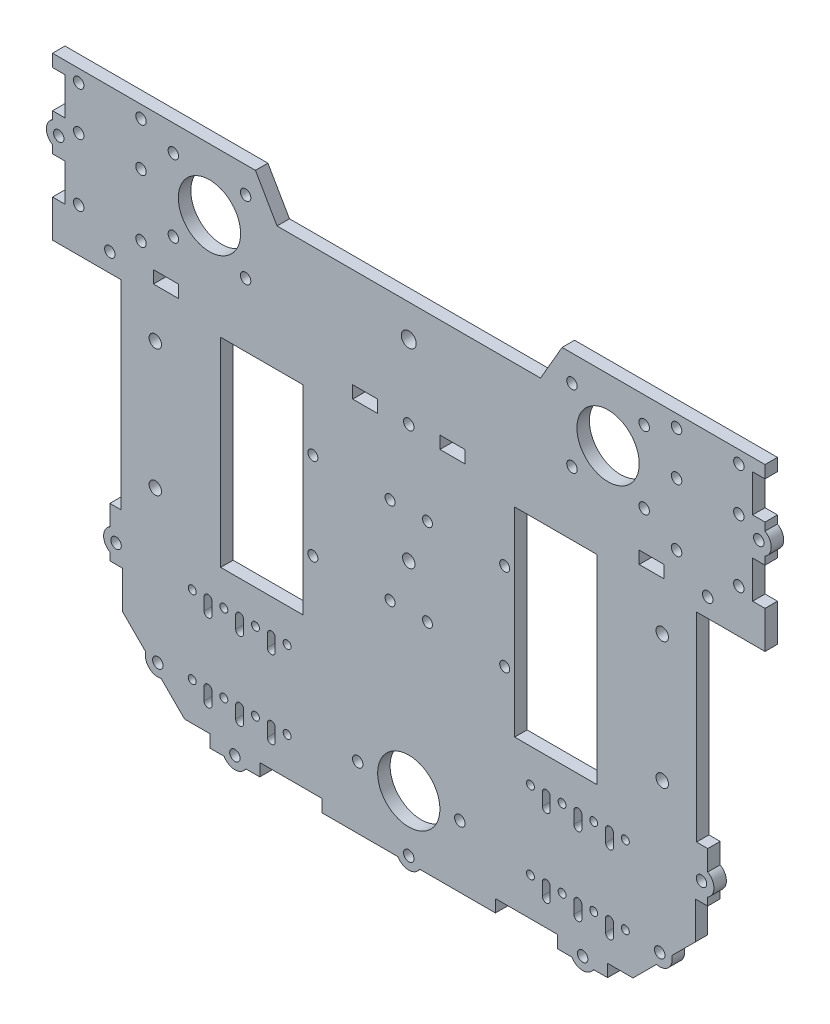
SolidWorks part; units mm, degrees
ref_plane "Front Plane" through (0, 0, 0) normal (0, 0, 1) x (1, 0, 0)
ref_plane "Top Plane" through (0, 0, 0) normal (0, 1, 0) x (1, 0, 0)
ref_plane "Right Plane" through (0, 0, 0) normal (1, 0, 0) x (0, 0, -1)
sketch "Sketch1" plane through (0, 0, 0) normal (0, 0, 1) x (1, 0, 0)
  line L1 (0, 0) -> (-240, 0)
  line L2 (0, 0) -> (0, 210)
  line L3 (0, 210) -> (-240, 210)
  line L4 (-240, 0) -> (-240, 210)
  dimension "D1" = 240
  dimension "D2" = 210
extrude "Boss-Extrude1" add sketch "Sketch1" along normal blind 5
sketch "Sketch2" plane through (0, 0, 5) normal (0, 0, 1) x (1, 0, 0)
  line L0 (-240, 210) -> (-240, 0) construction
  line L1 (-240, 145) -> (-162.5, 145)
  line L2 (-240, 145) -> (-240, 65)
  line L3 (-240, 65) -> (-162.5, 65)
  line L4 (-162.5, 145) -> (-162.5, 65)
  line L5 (-120, 210) -> (-120, 182.7983) construction
  line L6 (0, 210) -> (-240, 210) construction
  line L7 (-77.5, 145) -> (-77.5, 65)
  line L8 (0, 65) -> (-77.5, 65)
  line L9 (0, 145) -> (0, 65)
  line L10 (0, 145) -> (-77.5, 145)
  point P14 (-240, 105)
  point P15 (-162.5, 105)
  dimension "D1" = 80
  dimension "D2" = 77.5
extrude "Cut-Extrude1" cut sketch "Sketch2" against normal blind 5
sketch "Sketch3" plane through (0, 0, 5) normal (0, 0, 1) x (1, 0, 0)
  line L0 (-162.5, 145) -> (-240, 145) construction
  line L1 (-230.5, 145) -> (-213, 145)
  line L2 (-230.5, 145) -> (-230.5, 65)
  line L3 (-230.5, 65) -> (-213, 65)
  line L4 (-213, 145) -> (-213, 65)
  line L5 (-240, 65) -> (-162.5, 65) construction
  line L6 (-162.5, 65) -> (-162.5, 145) construction
  line L7 (-120, 210) -> (-120, 181.1057) construction
  line L8 (0, 210) -> (-240, 210) construction
  line L9 (-27, 145) -> (-27, 65)
  line L10 (-9.5, 65) -> (-27, 65)
  line L11 (-9.5, 145) -> (-9.5, 65)
  line L12 (-9.5, 145) -> (-27, 145)
  dimension "D1" = 17.5
  dimension "D2" = 68
extrude "Boss-Extrude2" add sketch "Sketch3" against normal blind 5
ref_plane "Plane1" through (-120, 0, 0) normal (1, 0, 0) x (0, 0, -1)
sketch "Sketch9" plane through (0, 0, 0) normal (0, 0, -1) x (-1, 0, 0)
  line L0 (240, 0) -> (0, 0) construction
  line L1 (170, 190) -> (220, 276.6025)
  line L2 (220, 276.6025) -> (170, 363.2051)
  line L3 (170, 363.2051) -> (70, 363.2051)
  line L4 (70, 363.2051) -> (20, 276.6025)
  line L5 (20, 276.6025) -> (70, 190)
  line L6 (70, 190) -> (170, 190)
  line L8 (0, 210) -> (240, 210) construction
  circle A0 centre (120, 276.6025) radius 86.6025 construction
  point P11 (120, 0)
  dimension "D1" = 200
  dimension "D2" = 20
extrude "Cut-Extrude8" cut sketch "Sketch9" against normal blind 5
sketch "Sketch10" plane through (-240, 0, 0) normal (-1, 0, 0) x (0, 0, 1)
  line L4 (0, 210) -> (0, 145)
  line L5 (0, 145) -> (5, 145)
  line L6 (5, 145) -> (5, 210)
  line L7 (5, 210) -> (0, 210)
  line L8 (0, 210) -> (0, 145)
  line L9 (0, 145) -> (5, 145)
  line L10 (5, 145) -> (5, 210)
  line L11 (5, 210) -> (0, 210)
  dimension "D1" = 0
extrude "Boss-Extrude3" add sketch "Sketch10" along normal blind 20
mirror "Mirror2" about plane through (-120, 0, 0) normal (1, 0, 0) of "Boss-Extrude3"
sketch "Sketch5" plane through (0, 0, 5) normal (0, 0, 1) x (1, 0, 0)
  line L0 (20, 210) -> (-58.453, 210) construction
  line L3 (12.5, 187.5) -> (0, 175) construction
  line L4 (0, 175) -> (-10.0719, 185.0719) construction
  line L5 (20, 210) -> (20, 145) construction
  circle A1 centre (0, 175) radius 11 construction
  circle A2 centre (12.5, 187.5) radius 2.1
  circle A5 centre (-12.5, 162.5) radius 2.1
  circle A6 centre (-12.5, 187.5) radius 2.1
  circle A7 centre (12.5, 162.5) radius 2.1
  circle A8 centre (12.5, 187.5) radius 2.1
  circle A9 centre (-12.5, 162.5) radius 2.1
  circle A10 centre (12.5, 162.5) radius 2.1
  circle A11 centre (-12.5, 187.5) radius 2.1
  circle A12 centre (-12.5, 205) radius 2.1
  circle A13 centre (12.5, 205) radius 2.1
  dimension "D1" = 35
  dimension "D2" = 12.5
  dimension "D3" = 12.5
  dimension "D4" = 22
  dimension "D5" = 4
  dimension "D6" = 4.2
  dimension "D7" = 5
  dimension "D8" = 20
  dimension "D9" = 5
  dimension "D10" = 4.2
  dimension "D11" = 4.2
  dimension "D12" = 12.5
  dimension "D13" = 12.5
extrude "Cut-Extrude9" cut sketch "Sketch5" against normal blind 10 contours A1 | A6 | A12 | A7 | A5 | A2 | A13 region at (-12.5, 162.5, 5) region at (-12.5, 187.5, 5) region at (12.5, 162.5, 5) region at (-12.5, 205, 5)
mirror "Mirror3" about plane through (-120, 0, 0) normal (1, 0, 0) of "Cut-Extrude9"
sketch "Sketch12" plane through (0, 0, 5) normal (0, 0, 1) x (1, 0, 0)
  line L0 (0, 0) -> (0, 65) construction
  line L1 (0, 10) -> (-5, 10)
  line L2 (0, 10) -> (0, 45.2)
  line L3 (0, 45.2) -> (-5, 45.2)
  line L4 (-5, 10) -> (-5, 45.2)
  line L5 (-240, 0) -> (0, 0) construction
  line L6 (-120, -2.75) -> (-120, 2.75) construction
  line L7 (-240, 45.2) -> (-235, 45.2)
  line L8 (-235, 10) -> (-235, 45.2)
  line L9 (-240, 10) -> (-235, 10)
  line L10 (-240, 10) -> (-240, 45.2)
  line L11 (-240, 65) -> (-240, 0) construction
  line L12 (-215, 0) -> (-154.8, 0)
  line L13 (-215, 0) -> (-215, 5)
  line L14 (-215, 5) -> (-154.8, 5)
  line L15 (-154.8, 0) -> (-154.8, 5)
  line L16 (-25, 5) -> (-85.2, 5)
  line L17 (-85.2, 0) -> (-85.2, 5)
  line L18 (-25, 0) -> (-85.2, 0)
  line L19 (-25, 0) -> (-25, 5)
  dimension "D1" = 35.2
  dimension "D2" = 5
  dimension "D3" = 10
  dimension "D4" = 5
  dimension "D5" = 60.2
  dimension "D6" = 25
extrude "Cut-Extrude11" cut sketch "Sketch12" against normal blind 10
sketch "Sketch15" plane through (0, 0, 0) normal (0, 0, -1) x (-1, 0, 0)
  line L0 (162.5, 105) -> (150.9995, 105) construction
  line L1 (162.5, 65) -> (162.5, 145) construction
  line L2 (143, 87.5) -> (143, 97.0195) construction
  line L3 (162.5, 65) -> (77.5, 65) construction
  line L4 (120, 65) -> (120, 101.8451) construction
  line L5 (97, 87.5) -> (97, 97.0195) construction
  line L6 (77.5, 105) -> (89.0005, 105) construction
  circle A0 centre (158.5, 87.5) radius 2
  circle A1 centre (158.5, 122.5) radius 2
  circle A2 centre (127.5, 122.5) radius 2
  circle A3 centre (127.5, 87.5) radius 2
  circle A4 centre (112.5, 87.5) radius 2
  circle A5 centre (112.5, 122.5) radius 2
  circle A6 centre (81.5, 122.5) radius 2
  circle A7 centre (81.5, 87.5) radius 2
  circle A8 centre (120, 105) radius 2.5
  point P6 (162.5, 105)
  dimension "D1" = 4
  dimension "D2" = 4
  dimension "D3" = 17.5
  dimension "D5" = 5
  dimension "D4" = 15.5
extrude "Cut-Extrude13" cut sketch "Sketch15" against normal blind 10
sketch "Sketch16" plane through (0, 0, 0) normal (0, 0, -1) x (-1, 0, 0)
  line L0 (27, 145) -> (9.5, 145) construction
  line L1 (9.5, 65) -> (27, 65) construction
  line L2 (18.25, 145) -> (18.25, 65) construction
  line L3 (18.25, 105) -> (30.55, 105) construction
  line L4 (120, 105) -> (120, 123.3727) construction
  line L5 (221.75, 105) -> (209.45, 105) construction
  circle A4 centre (18.25, 130.5) radius 2.5
  circle A5 centre (18.25, 79.5) radius 2.5
  circle A6 centre (221.75, 79.5) radius 2.5
  circle A7 centre (221.75, 130.5) radius 2.5
  point P12 (18.25, 105)
  dimension "D1" = 5
  dimension "D2" = 25.5
extrude "Cut-Extrude14" cut sketch "Sketch16" against normal blind 10
sketch "Sketch17" plane through (0, 0, 0) normal (0, 0, -1) x (-1, 0, 0)
  line L0 (40, 185) -> (57.7701, 167.2299) construction
  line L1 (-20, 210) -> (58.453, 210) construction
  line L2 (-20, 210) -> (-20, 145) construction
  line L3 (40, 185) -> (33.7078, 178.7078) construction
  line L4 (120, 190) -> (120, 162.3502) construction
  line L5 (70, 190) -> (170, 190) construction
  line L6 (200, 185) -> (206.2922, 178.7078) construction
  line L7 (200, 185) -> (182.2299, 167.2299) construction
  line L8 (200, 185) -> (206.2922, 178.7078) construction
  line L9 (200, 185) -> (182.2299, 167.2299) construction
  circle A0 centre (40, 185) radius 12.5
  circle A1 centre (54.4957, 170.5043) radius 2.1
  circle A2 centre (25.5043, 199.4957) radius 2.1
  circle A12 centre (54.4957, 199.4957) radius 2.1
  circle A13 centre (25.5043, 170.5043) radius 2.1
  circle A14 centre (54.4957, 170.5043) radius 2.1
  circle A15 centre (25.5043, 199.4957) radius 2.1
  circle A16 centre (25.5043, 170.5043) radius 2.1
  circle A17 centre (54.4957, 199.4957) radius 2.1
  circle A18 centre (185.5043, 199.4957) radius 2.1
  circle A19 centre (214.4957, 170.5043) radius 2.1
  circle A20 centre (214.4957, 199.4957) radius 2.1
  circle A21 centre (185.5043, 170.5043) radius 2.1
  circle A22 centre (214.4957, 170.5043) radius 2.1
  circle A23 centre (185.5043, 199.4957) radius 2.1
  circle A24 centre (200, 185) radius 12.5
  circle A25 centre (185.5043, 170.5043) radius 2.1
  circle A26 centre (214.4957, 199.4957) radius 2.1
  dimension "D1" = 25
  dimension "D2" = 4.2
  dimension "D3" = 20.5
  dimension "D4" = 25
  dimension "D5" = 60
  dimension "D6" = 45
  dimension "D7" = 4
extrude "Cut-Extrude15" cut sketch "Sketch17" against normal blind 5 contours A13 | A0 | A13 | A12 | A1 | A24 | A20 | A19 | A21 | A2 | A18 region at (-40, 185, 0) region at (-54.4957, 170.5043, 0) region at (-54.4957, 199.4957, 0) region at (-25.5043, 170.5043, 0) region at (-214.4957, 170.5043, 0) region at (-214.4957, 199.4957, 0) region at (-185.5043, 170.5043, 0) region at (-200, 185, 0)
sketch "Sketch18" plane through (0, 0, 5) normal (0, 0, 1) x (1, 0, 0)
  line L0 (-235, 30) -> (-210, 5)
  line L1 (-235, 10) -> (-235, 45.2) construction
  line L2 (-154.8, 5) -> (-215, 5) construction
  line L3 (-210, 5) -> (-235, 5)
  line L4 (-235, 5) -> (-235, 30)
  line L5 (-235, 10) -> (-240, 10)
  line L6 (-240, 10) -> (-240, 0)
  line L7 (-240, 0) -> (-215, 0)
  line L8 (-215, 0) -> (-215, 5)
  line L9 (-120, -2.75) -> (-120, 2.75) construction
  line L10 (-5, 5) -> (-5, 30)
  line L11 (-5, 30) -> (-30, 5)
  line L12 (-25, 0) -> (-25, 5)
  line L13 (0, 0) -> (-25, 0)
  line L14 (0, 10) -> (0, 0)
  line L15 (-5, 10) -> (0, 10)
  line L16 (-30, 5) -> (-5, 5)
  dimension "D1" = 25
  dimension "D2" = 25
extrude "Cut-Extrude17" cut sketch "Sketch18" against normal blind 10 contours L4 L3 L0 | L7 L8 L3 L4 L5 L6 | L11 L16 L10 | L16 L12 L13 L14 L15 L10 region at (-226.6667, 13.3333, 5) region at (-229.1667, 3.3333, 5) region at (-13.3333, 13.3333, 5) region at (-10.8333, 3.3333, 5)
sketch "Sketch19" plane through (0, 0, 0) normal (0, 0, -1) x (-1, 0, 0)
  line L0 (154.8, 0) -> (85.2, 0) construction
  line L1 (166.1126, 25) -> (84.2471, 25) construction
  line L2 (120, 25) -> (120, 31.0152) construction
  circle A0 centre (120, 25) radius 12.5
  circle A2 centre (99.5, 25) radius 2.1
  circle A4 centre (140.5, 25) radius 2.1
  point P4 (120, 0)
  dimension "D1" = 25
  dimension "D2" = 25
  dimension "D3" = 4.2
  dimension "D4" = 20.5
extrude "Cut-Extrude18" cut sketch "Sketch19" against normal blind 10
sketch "Sketch21" plane through (-260, 0, 0) normal (-1, 0, 0) x (0, 0, 1)
  line L4 (5, 210) -> (0, 210)
  line L5 (0, 210) -> (0, 145)
  line L6 (0, 145) -> (5, 145)
  line L7 (5, 145) -> (5, 210)
  line L8 (5, 210) -> (0, 210)
  line L9 (0, 210) -> (0, 145)
  line L10 (0, 145) -> (5, 145)
  line L11 (5, 145) -> (5, 210)
  dimension "D1" = 0
extrude "Cut-Extrude20" cut sketch "Sketch21" against normal blind 3
sketch "Sketch22" plane through (20, 0, 0) normal (1, 0, 0) x (0, 0, -1)
  line L4 (0, 210) -> (-5, 210)
  line L5 (-5, 210) -> (-5, 145)
  line L6 (-5, 145) -> (0, 145)
  line L7 (0, 145) -> (0, 210)
  line L8 (0, 210) -> (-5, 210)
  line L9 (-5, 210) -> (-5, 145)
  line L10 (-5, 145) -> (0, 145)
  line L11 (0, 145) -> (0, 210)
  dimension "D1" = 0
extrude "Cut-Extrude21" cut sketch "Sketch22" against normal blind 3
sketch "Sketch23" plane through (0, 0, 0) normal (0, 0, -1) x (-1, 0, 0)
  line L0 (154.8, 0) -> (85.2, 0) construction
  line L1 (124.3301, 0) -> (115.6699, 0) construction
  circle A0 centre (120, 2.5) radius 2.1
  arc A1 (124.3301, 0) -> (115.6699, 0) centre (120, 2.5) cw construction
  point P5 (120, 0)
  dimension "D1" = 4.2
  dimension "D2" = 2.5
  dimension "D3" = 5
extrude "Cut-Extrude22" cut sketch "Sketch23" against normal blind 10
sketch "Sketch24" plane through (0, 0, 0) normal (0, 0, -1) x (-1, 0, 0)
  line L0 (154.8, 0) -> (85.2, 0) construction
  line L1 (124.3301, 0) -> (115.6699, 0)
  arc A0 (124.3301, 0) -> (115.6699, 0) centre (120, 2.5) cw
  dimension "D1" = 5
extrude "Boss-Extrude4" add sketch "Sketch24" against normal blind 5
sketch "Sketch25" plane through (-17.5, 17.5, 0) normal (0.7071, -0.7071, 0) x (0, 0, -1)
  line L1 (12.2918, -37.7929) -> (-20.8331, -37.7929)
  line L2 (12.2918, -37.7929) -> (12.2918, 35.3561)
  line L3 (12.2918, 35.3561) -> (-20.8331, 35.3561)
  line L4 (-20.8331, -37.7929) -> (-20.8331, 35.3561)
ref_plane "Plane2" through (-120, 0, 0) normal (1, 0, 0) x (0, 0, -1)
sketch "Sketch26" plane through (0, 5, 0) normal (0, -1, 0) x (1, 0, 0)
  line L1 (-60.2, 5) -> (-40.2, 5)
  line L2 (-60.2, 5) -> (-60.2, 0)
  line L3 (-60.2, 0) -> (-40.2, 0)
  line L4 (-40.2, 5) -> (-40.2, 0)
  line L7 (-85.2, 0) -> (-85.2, 5) construction
  line L8 (-124.3301, 5) -> (-124.3301, 0) construction
  line L12 (-115.6699, 5) -> (-115.6699, 0) construction
  line L13 (-124.3301, 5) -> (-124.3301, 0) construction
  line L14 (-115.6699, 5) -> (-115.6699, 0) construction
  line L16 (-115.6699, 2.5) -> (-124.3301, 2.5) construction
  line L17 (-124.3301, 2.5) -> (-120, 2.5) construction
  line L18 (-120, 2.5) -> (-120, 11.7083) construction
  line L19 (-199.8, 5) -> (-199.8, 0)
  line L20 (-179.8, 0) -> (-199.8, 0)
  line L21 (-179.8, 5) -> (-179.8, 0)
  line L22 (-179.8, 5) -> (-199.8, 5)
  line M6 (-30, 5) -> (-85.2, 5)
  line M8 (-85.2, 0) -> (-30, 0)
  dimension "D1" = 20
  dimension "D2" = 25
extrude "Boss-Extrude5" add sketch "Sketch26" along normal blind 5 contours L4 L2 M6 M8 | L21 L22 L19 L20 region at (-50.2, 5, 2.5) region at (-189.8, 5, 2.5)
sketch "Sketch27" plane through (0, 0, 0) normal (0, 0, -1) x (-1, 0, 0)
  line L2 (120, 2.5) -> (120, 6.3371) construction
  circle A0 centre (50.2, 2.5) radius 2.1
  circle A1 centre (189.8, 2.5) radius 2.1
  dimension "D3" = 4.2
extrude "Cut-Extrude24" cut sketch "Sketch27" against normal blind 5
sketch "Sketch29" plane through (0, 0, 0) normal (0, 0, -1) x (-1, 0, 0)
  line L1 (194.1301, 0) -> (185.4699, 0)
  line L2 (120, 2.75) -> (120, -2.75) construction
  line L3 (45.8699, 0) -> (54.5301, 0)
  arc A0 (185.4699, 0) -> (194.1301, 0) centre (189.8, 2.5) ccw
  arc A1 (54.5301, 0) -> (45.8699, 0) centre (50.2, 2.5) cw
  dimension "D1" = 5
extrude "Boss-Extrude7" add sketch "Sketch29" against normal blind 5
sketch "Sketch30" plane through (-9.5, 0, 0) normal (1, 0, 0) x (0, 0, -1)
  line L4 (-5, 145) -> (-5, 65)
  line L5 (-5, 65) -> (0, 65)
  line L6 (0, 65) -> (0, 145)
  line L7 (0, 145) -> (-5, 145)
  line L8 (-5, 145) -> (-5, 65)
  line L9 (-5, 65) -> (0, 65)
  line L10 (0, 65) -> (0, 145)
  line L11 (0, 145) -> (-5, 145)
  dimension "D1" = 0
extrude "Boss-Extrude8" add sketch "Sketch30" along normal blind 5
sketch "Sketch31" plane through (-230.5, 0, 0) normal (-1, 0, 0) x (0, 0, 1)
  line L4 (5, 65) -> (5, 145)
  line L5 (5, 145) -> (0, 145)
  line L6 (0, 145) -> (0, 65)
  line L7 (0, 65) -> (5, 65)
  line L8 (5, 65) -> (5, 145)
  line L9 (5, 145) -> (0, 145)
  line L10 (0, 145) -> (0, 65)
  line L11 (0, 65) -> (5, 65)
  dimension "D1" = 0
extrude "Boss-Extrude9" add sketch "Sketch31" along normal blind 5
sketch "Sketch32" plane through (0, 0, 0) normal (0, 0, -1) x (-1, 0, 0)
  line L0 (5, 30) -> (30, 5) construction
  line L1 (17.5, 17.5) -> (24.3538, 24.3538) construction
  circle A0 centre (19.2678, 19.2678) radius 2.1
  dimension "D1" = 4.2
  dimension "D2" = 2.5
extrude "Cut-Extrude25" cut sketch "Sketch32" against normal blind 5
sketch "Sketch33" plane through (0, 0, 0) normal (0, 0, -1) x (-1, 0, 0)
  line L0 (5, 30) -> (30, 5) construction
  line L1 (20.5619, 14.4381) -> (14.4381, 20.5619)
  arc A0 (20.5619, 14.4381) -> (14.4381, 20.5619) centre (19.2678, 19.2678) cw
  dimension "D1" = 5
extrude "Boss-Extrude10" add sketch "Sketch33" against normal blind 5
ref_plane "Plane3" through (-120, 0, 0) normal (-1, 0, 0) x (0, 0, 1)
mirror "Mirror4" about plane through (-120, 0, 0) normal (-1, 0, 0) of "Boss-Extrude10", "Cut-Extrude25"
sketch "Sketch34" plane through (0, 0, 5) normal (0, 0, 1) x (1, 0, 0)
  line L2 (-70, 190) -> (-170, 190) construction
  circle A0 centre (-120, 182) radius 3
  point P4 (-120, 190)
  dimension "D1" = 6
  dimension "D3" = 8
extrude "Cut-Extrude26" cut sketch "Sketch34" against normal blind 5
sketch "Sketch35" plane through (0, 0, 0) normal (0, 0, -1) x (-1, 0, 0)
  line L0 (70, 190) -> (170, 190) construction
  line L1 (97.5, 155) -> (107.5, 155)
  line L2 (97.5, 155) -> (97.5, 150)
  line L3 (97.5, 150) -> (107.5, 150)
  line L4 (107.5, 155) -> (107.5, 150)
  line L5 (-17, 145) -> (-17, 210) construction
  line L6 (120, 190) -> (120, 169.3293) construction
  line L7 (132.5, 155) -> (132.5, 150)
  line L8 (142.5, 150) -> (132.5, 150)
  line L9 (142.5, 155) -> (142.5, 150)
  line L10 (142.5, 155) -> (132.5, 155)
  line L11 (107.5, 152.5) -> (132.5, 152.5) construction
  circle A0 centre (120, 152.5) radius 2.1
  point P6 (97.5, 152.5)
  dimension "D5" = 4.2
  dimension "D1" = 35
  dimension "D2" = 114.5
  dimension "D3" = 10
  dimension "D4" = 5
extrude "Cut-Extrude27" cut sketch "Sketch35" against normal blind 5
sketch "Sketch37" plane through (0, 45.2, 0) normal (0, -1, 0) x (1, 0, 0)
  line L4 (0, 0) -> (0, 5)
  line L5 (0, 5) -> (-5, 5)
  line L6 (-5, 5) -> (-5, 0)
  line L7 (-5, 0) -> (0, 0)
  line L8 (0, 0) -> (0, 5)
  line L9 (0, 5) -> (-5, 5)
  line L10 (-5, 5) -> (-5, 0)
  line L11 (-5, 0) -> (0, 0)
  dimension "D1" = 0
extrude "Boss-Extrude11" add sketch "Sketch37" along normal blind 0.2
sketch "Sketch38" plane through (0, 45.2, 0) normal (0, -1, 0) x (1, 0, 0)
  line L4 (-235, 0) -> (-235, 5)
  line L5 (-235, 5) -> (-240, 5)
  line L6 (-240, 5) -> (-240, 0)
  line L7 (-240, 0) -> (-235, 0)
  line L8 (-235, 0) -> (-235, 5)
  line L9 (-235, 5) -> (-240, 5)
  line L10 (-240, 5) -> (-240, 0)
  line L11 (-240, 0) -> (-235, 0)
  dimension "D1" = 0
extrude "Boss-Extrude12" add sketch "Sketch38" along normal blind 0.2
sketch "Sketch39" plane through (0, 0, 0) normal (0, 0, -1) x (-1, 0, 0)
  line L0 (5, 45) -> (0, 45) construction
  line L1 (0, 45) -> (0, 65) construction
  line L2 (120, 37.5) -> (120, 57.8422) construction
  line L3 (0, 56.8301) -> (0, 48.1699) construction
  line L4 (240, 56.8301) -> (240, 48.1699) construction
  circle A0 centre (2.5, 52.5) radius 2.1
  circle A1 centre (120, 25) radius 12.5 construction
  circle A2 centre (237.5, 52.5) radius 2.1
  arc A3 (0, 48.1699) -> (0, 56.8301) centre (2.5, 52.5) cw construction
  arc A4 (240, 48.1699) -> (240, 56.8301) centre (237.5, 52.5) ccw construction
  dimension "D1" = 4.2
  dimension "D2" = 7.5
  dimension "D3" = 2.5
  dimension "D4" = 5
extrude "Cut-Extrude28" cut sketch "Sketch39" against normal blind 5
sketch "Sketch40" plane through (0, 0, 0) normal (0, 0, -1) x (-1, 0, 0)
  line L0 (0, 45) -> (0, 65) construction
  line L1 (0, 56.8301) -> (0, 48.1699)
  line L2 (120, 37.5) -> (120, 52.5) construction
  line L3 (240, 56.8301) -> (240, 48.1699)
  arc A0 (0, 48.1699) -> (0, 56.8301) centre (2.5, 52.5) cw
  circle A1 centre (120, 25) radius 12.5 construction
  arc A2 (240, 48.1699) -> (240, 56.8301) centre (237.5, 52.5) ccw
  dimension "D1" = 5
extrude "Boss-Extrude13" add sketch "Sketch40" against normal blind 5
sketch "Sketch42" plane through (0, 0, 5) normal (0, 0, 1) x (1, 0, 0)
  line L0 (-81.5, 122.5) -> (-81.5, 87.5) construction
  line L1 (-81.5, 105) -> (-63.225, 105) construction
  line L2 (-71.1625, 51.5) -> (-71.1625, 20.25) construction
  line L3 (-71.1625, 35.875) -> (-81.5, 35.875) construction
  line L4 (-64.8125, 51.5) -> (-64.8125, 20.25) construction
  line L5 (-58.4625, 51.5) -> (-58.4625, 20.25) construction
  line L6 (-52.1125, 20.25) -> (-52.1125, 51.5) construction
  line L7 (-45.7625, 51.5) -> (-45.7625, 20.25) construction
  line L8 (-39.4125, 20.25) -> (-39.4125, 51.5) construction
  line L9 (-33.0625, 51.5) -> (-33.0625, 20.25) construction
  line L10 (17, 210) -> (17, 145) construction
  line L13 (17, 210) -> (-58.453, 210) construction
  line L14 (-64.8125, 51.5) -> (-64.8125, 46.5) construction
  line L15 (-63.225, 51.5) -> (-63.225, 46.5)
  line L16 (-66.4, 51.5) -> (-66.4, 46.5)
  line L17 (-52.1125, 51.5) -> (-52.1125, 46.5) construction
  line L18 (-50.525, 51.5) -> (-50.525, 46.5)
  line L19 (-53.7, 51.5) -> (-53.7, 46.5)
  line L20 (-39.4125, 51.5) -> (-39.4125, 46.5) construction
  line L21 (-37.825, 51.5) -> (-37.825, 46.5)
  line L22 (-41, 51.5) -> (-41, 46.5)
  line L23 (-64.8125, 20.25) -> (-64.8125, 15.25) construction
  line L24 (-63.225, 20.25) -> (-63.225, 15.25)
  line L25 (-66.4, 20.25) -> (-66.4, 15.25)
  line L26 (-52.1125, 20.25) -> (-52.1125, 15.25) construction
  line L27 (-50.525, 20.25) -> (-50.525, 15.25)
  line L28 (-53.7, 20.25) -> (-53.7, 15.25)
  line L29 (-39.4125, 20.25) -> (-39.4125, 15.25) construction
  line L30 (-37.825, 20.25) -> (-37.825, 15.25)
  line L31 (-41, 20.25) -> (-41, 15.25)
  line L32 (-120, -2.75) -> (-120, 2.75) construction
  line L33 (-206.9375, 51.5) -> (-206.9375, 20.25) construction
  line L34 (-200.5875, 20.25) -> (-200.5875, 51.5) construction
  line L35 (-194.2375, 51.5) -> (-194.2375, 20.25) construction
  line L36 (-187.8875, 20.25) -> (-187.8875, 51.5) construction
  line L37 (-181.5375, 51.5) -> (-181.5375, 20.25) construction
  line L38 (-175.1875, 51.5) -> (-175.1875, 20.25) construction
  line L39 (-168.8375, 35.875) -> (-158.5, 35.875) construction
  line L40 (-168.8375, 51.5) -> (-168.8375, 20.25) construction
  line L41 (-200.5875, 20.25) -> (-200.5875, 15.25) construction
  line L42 (-202.175, 20.25) -> (-202.175, 15.25)
  line L43 (-199, 20.25) -> (-199, 15.25)
  line L44 (-187.8875, 20.25) -> (-187.8875, 15.25) construction
  line L45 (-189.475, 20.25) -> (-189.475, 15.25)
  line L46 (-186.3, 20.25) -> (-186.3, 15.25)
  line L47 (-175.1875, 20.25) -> (-175.1875, 15.25) construction
  line L48 (-176.775, 20.25) -> (-176.775, 15.25)
  line L49 (-173.6, 20.25) -> (-173.6, 15.25)
  line L50 (-200.5875, 51.5) -> (-200.5875, 46.5) construction
  line L51 (-202.175, 51.5) -> (-202.175, 46.5)
  line L52 (-199, 51.5) -> (-199, 46.5)
  line L53 (-187.8875, 51.5) -> (-187.8875, 46.5) construction
  line L54 (-189.475, 51.5) -> (-189.475, 46.5)
  line L55 (-186.3, 51.5) -> (-186.3, 46.5)
  line L56 (-175.1875, 51.5) -> (-175.1875, 46.5) construction
  line L57 (-176.775, 51.5) -> (-176.775, 46.5)
  line L58 (-173.6, 51.5) -> (-173.6, 46.5)
  arc A2 (-63.225, 51.5) -> (-66.4, 51.5) centre (-64.8125, 51.5) ccw
  arc A3 (-66.4, 46.5) -> (-63.225, 46.5) centre (-64.8125, 46.5) ccw
  arc A4 (-50.525, 51.5) -> (-53.7, 51.5) centre (-52.1125, 51.5) ccw
  arc A5 (-53.7, 46.5) -> (-50.525, 46.5) centre (-52.1125, 46.5) ccw
  arc A6 (-37.825, 51.5) -> (-41, 51.5) centre (-39.4125, 51.5) ccw
  arc A7 (-41, 46.5) -> (-37.825, 46.5) centre (-39.4125, 46.5) ccw
  arc A8 (-63.225, 20.25) -> (-66.4, 20.25) centre (-64.8125, 20.25) ccw
  arc A9 (-66.4, 15.25) -> (-63.225, 15.25) centre (-64.8125, 15.25) ccw
  arc A10 (-50.525, 20.25) -> (-53.7, 20.25) centre (-52.1125, 20.25) ccw
  arc A11 (-53.7, 15.25) -> (-50.525, 15.25) centre (-52.1125, 15.25) ccw
  arc A12 (-37.825, 20.25) -> (-41, 20.25) centre (-39.4125, 20.25) ccw
  arc A13 (-41, 15.25) -> (-37.825, 15.25) centre (-39.4125, 15.25) ccw
  arc A14 (-179.95, 51.5) -> (-183.125, 51.5) centre (-181.5375, 51.5) cw
  arc A15 (-183.125, 51.5) -> (-179.95, 51.5) centre (-181.5375, 51.5) cw
  arc A16 (-173.6, 51.5) -> (-176.775, 51.5) centre (-175.1875, 51.5) cw
  arc A17 (-176.775, 51.5) -> (-173.6, 51.5) centre (-175.1875, 51.5) cw
  arc A18 (-167.25, 51.5) -> (-170.425, 51.5) centre (-168.8375, 51.5) cw
  arc A19 (-170.425, 51.5) -> (-167.25, 51.5) centre (-168.8375, 51.5) cw
  arc A20 (-189.475, 51.5) -> (-186.3, 51.5) centre (-187.8875, 51.5) cw
  arc A21 (-186.3, 51.5) -> (-189.475, 51.5) centre (-187.8875, 51.5) cw
  arc A22 (-195.825, 51.5) -> (-192.65, 51.5) centre (-194.2375, 51.5) cw
  arc A23 (-192.65, 51.5) -> (-195.825, 51.5) centre (-194.2375, 51.5) cw
  arc A24 (-202.175, 51.5) -> (-199, 51.5) centre (-200.5875, 51.5) cw
  arc A25 (-199, 51.5) -> (-202.175, 51.5) centre (-200.5875, 51.5) cw
  arc A26 (-205.35, 51.5) -> (-208.525, 51.5) centre (-206.9375, 51.5) cw
  arc A27 (-208.525, 51.5) -> (-205.35, 51.5) centre (-206.9375, 51.5) cw
  arc A28 (-69.575, 20.25) -> (-72.75, 20.25) centre (-71.1625, 20.25) ccw
  arc A29 (-72.75, 20.25) -> (-69.575, 20.25) centre (-71.1625, 20.25) ccw
  arc A30 (-63.225, 20.25) -> (-66.4, 20.25) centre (-64.8125, 20.25) ccw
  arc A31 (-66.4, 20.25) -> (-63.225, 20.25) centre (-64.8125, 20.25) ccw
  arc A32 (-56.875, 20.25) -> (-60.05, 20.25) centre (-58.4625, 20.25) ccw
  arc A33 (-60.05, 20.25) -> (-56.875, 20.25) centre (-58.4625, 20.25) ccw
  arc A34 (-50.525, 20.25) -> (-53.7, 20.25) centre (-52.1125, 20.25) ccw
  arc A35 (-53.7, 20.25) -> (-50.525, 20.25) centre (-52.1125, 20.25) ccw
  arc A36 (-44.175, 20.25) -> (-47.35, 20.25) centre (-45.7625, 20.25) ccw
  arc A37 (-47.35, 20.25) -> (-44.175, 20.25) centre (-45.7625, 20.25) ccw
  arc A38 (-37.825, 20.25) -> (-41, 20.25) centre (-39.4125, 20.25) ccw
  arc A39 (-41, 20.25) -> (-37.825, 20.25) centre (-39.4125, 20.25) ccw
  arc A40 (-31.475, 20.25) -> (-34.65, 20.25) centre (-33.0625, 20.25) ccw
  arc A41 (-34.65, 20.25) -> (-31.475, 20.25) centre (-33.0625, 20.25) ccw
  arc A42 (-31.475, 51.5) -> (-34.65, 51.5) centre (-33.0625, 51.5) ccw
  arc A43 (-34.65, 51.5) -> (-31.475, 51.5) centre (-33.0625, 51.5) ccw
  arc A44 (-41, 51.5) -> (-37.825, 51.5) centre (-39.4125, 51.5) ccw
  arc A45 (-37.825, 51.5) -> (-41, 51.5) centre (-39.4125, 51.5) ccw
  arc A46 (-47.35, 51.5) -> (-44.175, 51.5) centre (-45.7625, 51.5) ccw
  arc A47 (-44.175, 51.5) -> (-47.35, 51.5) centre (-45.7625, 51.5) ccw
  arc A48 (-53.7, 51.5) -> (-50.525, 51.5) centre (-52.1125, 51.5) ccw
  arc A49 (-50.525, 51.5) -> (-53.7, 51.5) centre (-52.1125, 51.5) ccw
  arc A50 (-69.575, 51.5) -> (-72.75, 51.5) centre (-71.1625, 51.5) ccw
  arc A51 (-72.75, 51.5) -> (-69.575, 51.5) centre (-71.1625, 51.5) ccw
  arc A52 (-63.225, 51.5) -> (-66.4, 51.5) centre (-64.8125, 51.5) ccw
  arc A53 (-66.4, 51.5) -> (-63.225, 51.5) centre (-64.8125, 51.5) ccw
  arc A54 (-56.875, 51.5) -> (-60.05, 51.5) centre (-58.4625, 51.5) ccw
  arc A55 (-60.05, 51.5) -> (-56.875, 51.5) centre (-58.4625, 51.5) ccw
  arc A56 (-205.35, 20.25) -> (-208.525, 20.25) centre (-206.9375, 20.25) cw
  arc A57 (-208.525, 20.25) -> (-205.35, 20.25) centre (-206.9375, 20.25) cw
  arc A58 (-199, 20.25) -> (-202.175, 20.25) centre (-200.5875, 20.25) cw
  arc A59 (-202.175, 20.25) -> (-199, 20.25) centre (-200.5875, 20.25) cw
  arc A60 (-192.65, 20.25) -> (-195.825, 20.25) centre (-194.2375, 20.25) cw
  arc A61 (-195.825, 20.25) -> (-192.65, 20.25) centre (-194.2375, 20.25) cw
  arc A62 (-186.3, 20.25) -> (-189.475, 20.25) centre (-187.8875, 20.25) cw
  arc A63 (-189.475, 20.25) -> (-186.3, 20.25) centre (-187.8875, 20.25) cw
  arc A64 (-179.95, 20.25) -> (-183.125, 20.25) centre (-181.5375, 20.25) cw
  arc A65 (-183.125, 20.25) -> (-179.95, 20.25) centre (-181.5375, 20.25) cw
  arc A66 (-173.6, 20.25) -> (-176.775, 20.25) centre (-175.1875, 20.25) cw
  arc A67 (-176.775, 20.25) -> (-173.6, 20.25) centre (-175.1875, 20.25) cw
  arc A68 (-167.25, 20.25) -> (-170.425, 20.25) centre (-168.8375, 20.25) cw
  arc A69 (-170.425, 20.25) -> (-167.25, 20.25) centre (-168.8375, 20.25) cw
  arc A70 (-202.175, 20.25) -> (-199, 20.25) centre (-200.5875, 20.25) cw
  arc A71 (-199, 15.25) -> (-202.175, 15.25) centre (-200.5875, 15.25) cw
  arc A72 (-189.475, 20.25) -> (-186.3, 20.25) centre (-187.8875, 20.25) cw
  arc A73 (-186.3, 15.25) -> (-189.475, 15.25) centre (-187.8875, 15.25) cw
  arc A74 (-176.775, 20.25) -> (-173.6, 20.25) centre (-175.1875, 20.25) cw
  arc A75 (-173.6, 15.25) -> (-176.775, 15.25) centre (-175.1875, 15.25) cw
  arc A76 (-202.175, 51.5) -> (-199, 51.5) centre (-200.5875, 51.5) cw
  arc A77 (-199, 46.5) -> (-202.175, 46.5) centre (-200.5875, 46.5) cw
  arc A78 (-189.475, 51.5) -> (-186.3, 51.5) centre (-187.8875, 51.5) cw
  arc A79 (-186.3, 46.5) -> (-189.475, 46.5) centre (-187.8875, 46.5) cw
  arc A80 (-176.775, 51.5) -> (-173.6, 51.5) centre (-175.1875, 51.5) cw
  arc A81 (-173.6, 46.5) -> (-176.775, 46.5) centre (-175.1875, 46.5) cw
  point P22 (-64.8125, 35.875)
  point P23 (-58.4625, 35.875)
  point P28 (-52.1125, 35.875)
  point P29 (-45.7625, 35.875)
  point P34 (-39.4125, 35.875)
  point P35 (-33.0625, 35.875)
  point P52 (-64.8125, 49)
  point P70 (-52.1125, 49)
  point P86 (-39.4125, 49)
  point P92 (-64.8125, 17.75)
  point P98 (-52.1125, 17.75)
  point P104 (-39.4125, 17.75)
  point P158 (-200.5875, 17.75)
  point P162 (-187.8875, 17.75)
  point P166 (-175.1875, 17.75)
  point P170 (-200.5875, 49)
  point P174 (-187.8875, 49)
  point P178 (-175.1875, 49)
  dimension "D1" = 1.5875
  dimension "D10" = 31.25
  dimension "D2" = 36
  dimension "D3" = 50.0625
  dimension "D4" = 56.4125
  dimension "D5" = 62.7625
  dimension "D6" = 69.1125
  dimension "D7" = 75.4625
  dimension "D8" = 81.8125
  dimension "D9" = 88.1625
  dimension "D11" = 5
  dimension "D12" = 5
extrude "Cut-Extrude29" cut sketch "Sketch42" against normal blind 10 contours A6 A44 | A44 L22 A7 L21 | A46 A47 | A4 A48 | A54 A55 | A2 A53 | A50 A51 | A53 L16 A3 L15 | A48 L19 A5 L18 | A43 A42 | A41 A40 | L30 A13 L31 A12 | A37 A36 | L28 A11 L27 A10 | A33 A32 | L25 A9 L24 A8 | A29 A28 region at (-64.8125, 51.5, 5) region at (-64.8125, 47.7532, 5) region at (-52.1125, 51.5, 5) region at (-52.1125, 47.7532, 5) region at (-39.4125, 51.5, 5) region at (-39.4125, 47.7532, 5) region at (-45.7625, 51.5, 5) region at (-71.1625, 51.5, 5) region at (-58.4625, 51.5, 5)
sketch "Sketch43" plane through (-257, 0, 0) normal (-1, 0, 0) x (0, 0, 1)
  line L4 (5, 145) -> (5, 210)
  line L5 (5, 210) -> (0, 210)
  line L6 (0, 210) -> (0, 145)
  line L7 (0, 145) -> (5, 145)
  line L8 (5, 145) -> (5, 210)
  line L9 (5, 210) -> (0, 210)
  line L10 (0, 210) -> (0, 145)
  line L11 (0, 145) -> (5, 145)
  dimension "D1" = 0
extrude "Boss-Extrude14" add sketch "Sketch43" along normal blind 6
sketch "Sketch44" plane through (17, 0, 0) normal (1, 0, 0) x (0, 0, -1)
  line L4 (0, 145) -> (0, 210)
  line L5 (0, 210) -> (-5, 210)
  line L6 (-5, 210) -> (-5, 145)
  line L7 (-5, 145) -> (0, 145)
  line L8 (0, 145) -> (0, 210)
  line L9 (0, 210) -> (-5, 210)
  line L10 (-5, 210) -> (-5, 145)
  line L11 (-5, 145) -> (0, 145)
  dimension "D1" = 0
extrude "Boss-Extrude15" add sketch "Sketch44" along normal blind 6
sketch "Sketch45" plane through (0, 210, 0) normal (0, 1, 0) x (1, 0, 0)
  line L4 (-181.547, 0) -> (-263, 0)
  line L5 (-263, 0) -> (-263, -5)
  line L6 (-263, -5) -> (-181.547, -5)
  line L7 (-181.547, -5) -> (-181.547, 0)
  line L8 (-181.547, 0) -> (-263, 0)
  line L9 (-263, 0) -> (-263, -5)
  line L10 (-263, -5) -> (-181.547, -5)
  line L11 (-181.547, -5) -> (-181.547, 0)
  dimension "D1" = 0
extrude "Boss-Extrude16" [suppressed] add sketch "Sketch45" along normal blind 6
sketch "Sketch46" plane through (0, 210, 0) normal (0, 1, 0) x (1, 0, 0)
  line L4 (-58.453, -5) -> (23, -5)
  line L5 (23, -5) -> (23, 0)
  line L6 (23, 0) -> (-58.453, 0)
  line L7 (-58.453, 0) -> (-58.453, -5)
  line L8 (-58.453, -5) -> (23, -5)
  line L9 (23, -5) -> (23, 0)
  line L10 (23, 0) -> (-58.453, 0)
  line L11 (-58.453, 0) -> (-58.453, -5)
  dimension "D1" = 0
extrude "Boss-Extrude17" [suppressed] add sketch "Sketch46" along normal blind 6
sketch "Sketch47" [suppressed] plane through (0, 0, 5) normal (0, 0, 1) x (1, 0, 0)
  line L0 (-181.547, 210) -> (-185.0111, 216)
  line L1 (-263, 216) -> (-181.547, 216) construction
  line L2 (-185.0111, 216) -> (-181.547, 216)
  line L3 (-181.547, 216) -> (-181.547, 210)
  line L4 (-120, 182) -> (-120, 205.4993) construction
  line L5 (-58.453, 216) -> (-58.453, 210)
  line L6 (-54.9889, 216) -> (-58.453, 216)
  line L7 (-58.453, 210) -> (-54.9889, 216)
extrude "Cut-Extrude30" [suppressed] cut sketch "Sketch47" against normal blind 6
sketch "Sketch48" plane through (-213, 0, 0) normal (1, 0, 0) x (0, 0, -1)
  line L4 (-5, 145) -> (-5, 65)
  line L5 (-5, 65) -> (0, 65)
  line L6 (0, 65) -> (0, 145)
  line L7 (0, 145) -> (-5, 145)
  line L8 (-5, 145) -> (-5, 65)
  line L9 (-5, 65) -> (0, 65)
  line L10 (0, 65) -> (0, 145)
  line L11 (0, 145) -> (-5, 145)
  dimension "D1" = 0
extrude "Boss-Extrude18" [suppressed] add sketch "Sketch48" along normal blind 10
sketch "Sketch49" plane through (-27, 0, 0) normal (-1, 0, 0) x (0, 0, 1)
  line L4 (5, 65) -> (5, 145)
  line L5 (5, 145) -> (0, 145)
  line L6 (0, 145) -> (0, 65)
  line L7 (0, 65) -> (5, 65)
  line L8 (5, 65) -> (5, 145)
  line L9 (5, 145) -> (0, 145)
  line L10 (0, 145) -> (0, 65)
  line L11 (0, 65) -> (5, 65)
  dimension "D1" = 0
extrude "Boss-Extrude19" [suppressed] add sketch "Sketch49" along normal blind 10
sketch "Sketch50" [suppressed] plane through (0, 0, 5) normal (0, 0, 1) x (1, 0, 0)
  line L0 (23, 216) -> (23, 145) construction
  line L1 (23, 188.5) -> (18, 188.5)
  line L2 (23, 188.5) -> (23, 208.5)
  line L3 (23, 208.5) -> (18, 208.5)
  line L4 (18, 188.5) -> (18, 208.5)
  line L5 (-54.9889, 216) -> (23, 216) construction
  line L6 (18, 210.05) -> (18, 156.25) construction
  line L7 (23, 158.5) -> (18, 158.5)
  line L8 (23, 158.5) -> (23, 178.5)
  line L9 (23, 178.5) -> (18, 178.5)
  line L10 (18, 158.5) -> (18, 178.5)
  dimension "D1" = 5
  dimension "D2" = 7.5
  dimension "D3" = 20
  dimension "D4" = 20
  dimension "D5" = 10
extrude "Cut-Extrude31" [suppressed] cut sketch "Sketch50" against normal blind 5
ref_plane "Plane4" through (-120, 0, 0) normal (1, 0, 0) x (0, 0, -1)
mirror "Mirror5" [suppressed] about plane through (-120, 0, 0) normal (1, 0, 0)
sketch "Sketch51" [suppressed] plane through (0, 0, 5) normal (0, 0, 1) x (1, 0, 0)
  line L0 (-37, 65) -> (-37, 145) construction
  line L1 (-17.5, 150) -> (-27.5, 150)
  line L2 (-17.5, 150) -> (-17.5, 155)
  line L3 (-17.5, 155) -> (-27.5, 155)
  line L4 (-27.5, 150) -> (-27.5, 155)
  line L5 (-37, 145) -> (-77.5, 145) construction
  line L6 (-120, 190) -> (-120, 166.8051) construction
  line L7 (-70, 190) -> (-170, 190) construction
  line L8 (-212.5, 150) -> (-212.5, 155)
  line L9 (-222.5, 155) -> (-212.5, 155)
  line L10 (-222.5, 150) -> (-222.5, 155)
  line L11 (-222.5, 150) -> (-212.5, 150)
  dimension "D1" = 10
  dimension "D2" = 5
  dimension "D3" = 9.5
  dimension "D4" = 5
extrude "Cut-Extrude32" [suppressed] cut sketch "Sketch51" against normal blind 5
sketch "Sketch52" [suppressed] plane through (0, 216, 0) normal (0, 1, 0) x (1, 0, 0)
  line L4 (-185.0111, -5) -> (-185.0111, 0)
  line L5 (-185.0111, 0) -> (-263, 0)
  line L6 (-263, 0) -> (-263, -5)
  line L7 (-263, -5) -> (-185.0111, -5)
  line L8 (-185.0111, -5) -> (-185.0111, 0)
  line L9 (-185.0111, 0) -> (-263, 0)
  line L10 (-263, 0) -> (-263, -5)
  line L11 (-263, -5) -> (-185.0111, -5)
  line L12 (-54.9889, 0) -> (-54.9889, -5)
  line L13 (-54.9889, -5) -> (23, -5)
  line L14 (23, -5) -> (23, 0)
  line L15 (23, 0) -> (-54.9889, 0)
  line L16 (-54.9889, 0) -> (-54.9889, -5)
  line L17 (-54.9889, -5) -> (23, -5)
  line L18 (23, -5) -> (23, 0)
  line L19 (23, 0) -> (-54.9889, 0)
  dimension "D1" = 0
  dimension "D2" = 0
extrude "Boss-Extrude20" [suppressed] add sketch "Sketch52" along normal blind 5
sketch "Sketch53" [suppressed] plane through (0, 0, 5) normal (0, 0, 1) x (1, 0, 0)
  line L0 (-185.0111, 216) -> (-187.8979, 221)
  line L1 (-263, 221) -> (-185.0111, 221) construction
  line L2 (-187.8979, 221) -> (-185.0111, 221)
  line L3 (-185.0111, 221) -> (-185.0111, 216)
  line L4 (-120, 190) -> (-120, 205.7472) construction
  line L5 (-70, 190) -> (-170, 190) construction
  line L6 (-54.9889, 221) -> (-54.9889, 216)
  line L7 (-52.1021, 221) -> (-54.9889, 221)
  line L8 (-54.9889, 216) -> (-52.1021, 221)
extrude "Cut-Extrude33" [suppressed] cut sketch "Sketch53" against normal blind 5
sketch "Sketch54" plane through (0, 0, 0) normal (0, 0, -1) x (-1, 0, 0)
  line L0 (27, 145) -> (77.5, 145) construction
  line L1 (17.5, 155) -> (27.5, 155)
  line L2 (17.5, 155) -> (17.5, 150)
  line L3 (17.5, 150) -> (27.5, 150)
  line L4 (27.5, 155) -> (27.5, 150)
  line L5 (4.5, 65) -> (4.5, 145) construction
  line L6 (120, 152.5) -> (120, 138.2924) construction
  line L7 (212.5, 155) -> (212.5, 150)
  line L8 (222.5, 150) -> (212.5, 150)
  line L9 (222.5, 155) -> (222.5, 150)
  line L10 (222.5, 155) -> (212.5, 155)
  dimension "D1" = 10
  dimension "D2" = 5
  dimension "D3" = 5
  dimension "D4" = 13
extrude "Cut-Extrude34" cut sketch "Sketch54" against normal blind 5
sketch "Sketch55" [suppressed] plane through (0, 221, 0) normal (0, 1, 0) x (1, 0, 0)
  line L0 (-52.1021, -5) -> (23, -5) construction
  line L1 (23, 0) -> (13, 0)
  line L2 (23, 0) -> (23, -5)
  line L3 (23, -5) -> (13, -5)
  line L4 (13, 0) -> (13, -5)
  line L5 (23, 0) -> (-52.1021, 0) construction
  line L6 (-7, 0) -> (-17, 0)
  line L7 (-7, 0) -> (-7, -5)
  line L8 (-7, -5) -> (-17, -5)
  line L9 (-17, 0) -> (-17, -5)
  line L10 (-70, -5) -> (-170, -5) construction
  line L11 (-70, -5) -> (-170, -5)
  line L12 (-120, -5) -> (-120, 10.6636) construction
  line L13 (-223, 0) -> (-223, -5)
  line L14 (-233, -5) -> (-223, -5)
  line L15 (-233, 0) -> (-233, -5)
  line L16 (-233, 0) -> (-223, 0)
  line L17 (-253, 0) -> (-253, -5)
  line L18 (-263, -5) -> (-253, -5)
  line L19 (-263, 0) -> (-263, -5)
  line L20 (-263, 0) -> (-253, 0)
  line M7 (-52.1021, -5) -> (23, -5)
  line M8 (23, -5) -> (23, 0)
  line M9 (23, 0) -> (-52.1021, 0)
  dimension "D1" = 10
  dimension "D2" = 10
  dimension "D3" = 20
extrude "Cut-Extrude35" [suppressed] cut sketch "Sketch55" against normal blind 5 contours L9 L7 M9 M7 | L4 M9 M7 M8 | L16 L15 L14 L13 | L20 L19 L18 L17
sketch "Sketch56" plane through (0, 0, 0) normal (0, 0, -1) x (-1, 0, 0)
  line L0 (-23, 145) -> (-23, 210) construction
  line L1 (-23, 210) -> (58.453, 210) construction
  line L2 (-23, 160) -> (-18.0205, 160)
  line L3 (-23, 160) -> (-23, 175)
  line L4 (-23, 175) -> (-18.0205, 175)
  line L5 (-18.0205, 160) -> (-18.0205, 175)
  line L6 (-23, 190) -> (-18.0205, 190)
  line L7 (-23, 190) -> (-23, 205)
  line L8 (-23, 205) -> (-18.0205, 205)
  line L9 (-18.0205, 190) -> (-18.0205, 205)
  dimension "D1" = 15
  dimension "D2" = 15
  dimension "D3" = 15
  dimension "D4" = 5
extrude "Cut-Extrude36" cut sketch "Sketch56" against normal blind 5
mirror "Mirror6" about plane through (-120, 0, 0) normal (1, 0, 0) of "Cut-Extrude36"
sketch "Sketch57" plane through (0, 0, 0) normal (0, 0, -1) x (-1, 0, 0)
  line L0 (222.5, 150) -> (222.5, 155) construction
  line L1 (222.5, 155) -> (212.5, 155) construction
  line L2 (120, 150.4) -> (120, 136.6161) construction
  circle A0 centre (240, 152.5) radius 2.1
  circle A1 centre (120, 152.5) radius 2.1 construction
  circle A2 centre (0, 152.5) radius 2.1
  dimension "D1" = 4.2
  dimension "D2" = 17.5
  dimension "D3" = 2.5
extrude "Cut-Extrude37" cut sketch "Sketch57" against normal blind 10
sketch "Sketch58" plane through (0, 0, 5) normal (0, 0, 1) x (1, 0, 0)
  line L0 (23, 190) -> (23, 175) construction
  line L1 (23, 190) -> (18.0205, 190) construction
  line L2 (-120, 190) -> (-120, 213.617) construction
  line L3 (-70, 190) -> (-170, 190) construction
  circle A0 centre (20.5, 182.5) radius 2.1
  circle A1 centre (-260.5, 182.5) radius 2.1
  dimension "D1" = 4.2
  dimension "D2" = 2.5
  dimension "D3" = 7.5
extrude "Cut-Extrude38" cut sketch "Sketch58" against normal blind 5
sketch "Sketch59" plane through (0, 0, 0) normal (0, 0, -1) x (-1, 0, 0)
  line L0 (263, 190) -> (263, 175) construction
  line L1 (263, 186.8301) -> (263, 178.1699)
  line L2 (120, 182) -> (120, 164.0179) construction
  line L3 (-23, 186.8301) -> (-23, 178.1699)
  arc A0 (263, 178.1699) -> (263, 186.8301) centre (260.5, 182.5) ccw
  arc A1 (-23, 178.1699) -> (-23, 186.8301) centre (-20.5, 182.5) cw
  dimension "D1" = 5
extrude "Boss-Extrude21" add sketch "Sketch59" against normal blind 5
mirror "Mirror7" about plane through (-120, 0, 0) normal (1, 0, 0) of "Cut-Extrude29"
sketch "Sketch60" plane through (-27, 0, 0) normal (-1, 0, 0) x (0, 0, 1)
  line L4 (5, 65) -> (5, 145)
  line L5 (5, 145) -> (0, 145)
  line L6 (0, 145) -> (0, 65)
  line L7 (0, 65) -> (5, 65)
  line L8 (5, 65) -> (5, 145)
  line L9 (5, 145) -> (0, 145)
  line L10 (0, 145) -> (0, 65)
  line L11 (0, 65) -> (5, 65)
  dimension "D1" = 0
extrude "Boss-Extrude22" add sketch "Sketch60" along normal blind 17.5
sketch "Sketch61" plane through (-213, 0, 0) normal (1, 0, 0) x (0, 0, -1)
  line L4 (-5, 145) -> (-5, 65)
  line L5 (-5, 65) -> (0, 65)
  line L6 (0, 65) -> (0, 145)
  line L7 (0, 145) -> (-5, 145)
  line L8 (-5, 145) -> (-5, 65)
  line L9 (-5, 65) -> (0, 65)
  line L10 (0, 65) -> (0, 145)
  line L11 (0, 145) -> (-5, 145)
  dimension "D1" = 0
extrude "Boss-Extrude23" add sketch "Sketch61" along normal blind 17.5
sketch "Sketch62" plane through (0, 0, 5) normal (0, 0, 1) x (1, 0, 0)
  line L0 (-70, 190) -> (-170, 190)
  line L1 (-170, 190) -> (-172.8868, 195)
  line L2 (-170, 190) -> (-181.547, 210) construction
  line L3 (-172.8868, 195) -> (-67.1132, 195)
  line L4 (-58.453, 210) -> (-70, 190) construction
  line L5 (-67.1132, 195) -> (-70, 190)
  dimension "D1" = 5
extrude "Boss-Extrude24" add sketch "Sketch62" against normal blind 5
